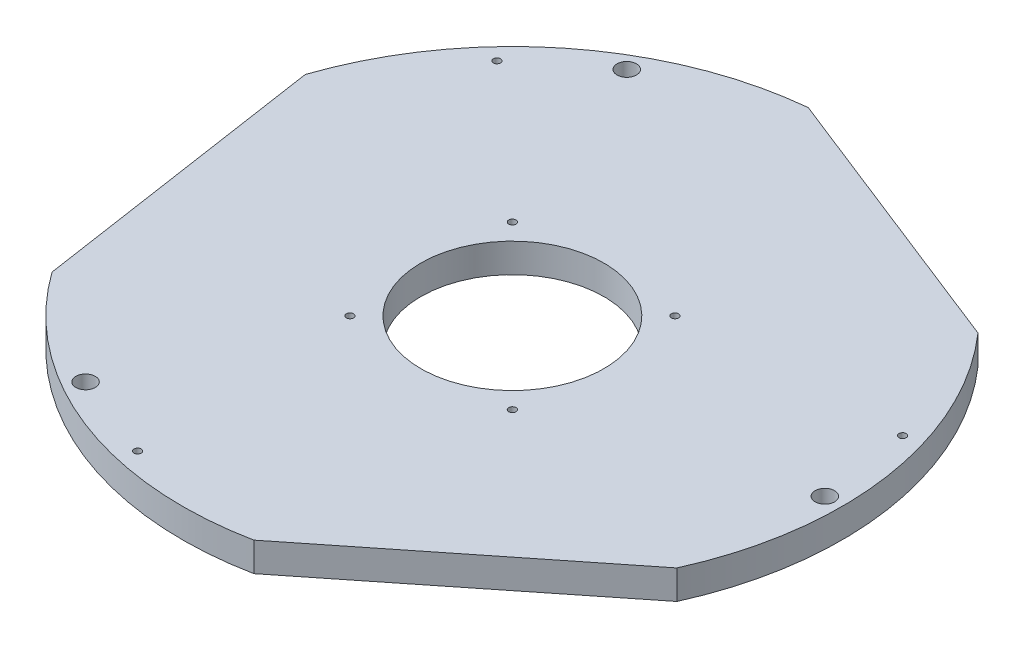
SolidWorks part; units mm, degrees
material "Oak"
ref_plane "Front Plane" through (0, 0, 0) normal (0, 0, 1) x (1, 0, 0)
ref_plane "Top Plane" through (0, 0, 0) normal (0, 1, 0) x (1, 0, 0)
ref_plane "Right Plane" through (0, 0, 0) normal (1, 0, 0) x (0, 0, -1)
sketch "Sketch1" plane through (0, 0, 0) normal (0, 0, 1) x (1, 0, 0)
  line L0 (0, -200000) -> (0, 218797.9879) construction
  line L1 (144.145, -22.3802) -> (144.145, -35.0802) construction
  line L2 (0, -22.3802) -> (144.145, -22.3802) construction
  line L3 (144.145, -35.0802) -> (0, -35.0802) construction
  line L4 (0, -200000) -> (0, 218797.9879) construction
  line L5 (144.145, -22.3802) -> (144.145, -35.0802)
  line L6 (0, -22.3802) -> (144.145, -22.3802)
  line L7 (144.145, -35.0802) -> (0, -35.0802)
  line L8 (0, -22.3802) -> (0, -35.0802)
revolve "Revolve1" add sketch "Sketch1" angle 360 about L4
hole_wizard "1/8 (0.125) Diameter Hole1" positions "Sketch2" profile "Sketch3" hole size "1/8" standard "ANSI Inch" end condition up to next
sketch "Sketch2" plane through (0, -22.3802, 0) normal (0, 1, 0) x (1, 0, 0)
  line L0 (0, 0) -> (136.525, 0) construction
  line L3 (0, 0) -> (-68.2625, -118.2341) construction
  line L6 (0, 0) -> (-68.2625, 118.2341) construction
  line L7 (-99.8481, 93.1098) -> (0, 0) construction
  line L9 (0, 0) -> (-30.7114, -133.0259) construction
  line L12 (0, 0) -> (130.5595, 39.916) construction
  line L14 (-35.5, -35.5) -> (35.5, -35.5) construction
  line L15 (-35.5, -35.5) -> (-35.5, 35.5) construction
  line L16 (-35.5, 35.5) -> (35.5, 35.5) construction
  line L17 (35.5, -35.5) -> (35.5, 35.5) construction
  line L18 (-35.5, 0) -> (0, 0) construction
  line L19 (0, 0) -> (0, -35.5) construction
  circle A0 centre (0, 0) radius 136.525
  point P0 (136.525, 0)
  point P2 (-68.2625, -118.2341)
  point P4 (-68.2625, 118.2341)
  point P32 (-99.8481, 93.1098)
  point P57 (130.5595, 39.916)
  point P60 (-30.7114, -133.0259)
  point P138 (-35.5, -35.5)
  point P141 (-35.5, 35.5)
  point P144 (35.5, 35.5)
  point P147 (35.5, -35.5)
  dimension "D3" = 17
  dimension "D1" = 120
  dimension "D2" = 120
  dimension "D4" = 120
  dimension "D5" = 120
  dimension "D6" = 71
sketch "Sketch3" plane through (136.525, -22.3802, 0) normal (1, 0, 0) x (0, 0, 1)
  line L0 (0, 0) -> (0, 12.7)
  line L1 (0, 12.7) -> (1.5875, 12.7)
  line L2 (1.5875, 12.7) -> (1.5875, 0)
  line L5 (1.5875, 0) -> (0, 0)
  line L11 (0, -6.35) -> (0, 107.95) construction
  dimension "Thru Hole Dia." = 3.175
  dimension "Thru Hole Depth" = 12.7
sketch "Sketch4" plane through (0, -22.3802, 0) normal (0, 1, 0) x (1, 0, 0)
  line L0 (253.7221, 37.919) -> (-94.0222, -238.6893)
  line L1 (-94.0222, -238.6893) -> (-159.6999, 200.7703)
  line L2 (-159.6999, 200.7703) -> (253.7221, 37.919)
  line L3 (253.7221, 37.919) -> (0, 0) construction
  line L4 (130.5595, 39.916) -> (136.525, 0) construction
  circle A0 centre (0, 0) radius 128.27 construction
  point P6 (133.5423, 19.958)
  dimension "D1" = 256.54
extrude "Cut-Extrude1" cut sketch "Sketch4" against normal through all flip side to cut
sketch "Sketch6" plane through (0, -22.3802, 0) normal (0, 1, 0) x (1, 0, 0)
  circle A0 centre (0, 0) radius 40
  dimension "D1" = 80
extrude "Cut-Extrude2" cut sketch "Sketch6" against normal through all
hole_wizard "M10x1.5 Tapped Hole1" positions "Sketch7" profile "Sketch8" tap size "M10x1.5" standard "ANSI Metric" end condition through all
sketch "Sketch7" plane through (0, -22.3802, 0) normal (0, 1, 0) x (1, 0, 0)
  point P0 (-68.2625, 118.2341)
  point P4 (136.525, 0)
  point P8 (-68.2625, -118.2341)
sketch "Sketch8" plane through (-68.2625, -22.3802, -118.2341) normal (1, 0, 0) x (0, 0, 1)
  line L0 (0, 0) -> (0, 12.7)
  line L1 (0, 12.7) -> (4.25, 12.7)
  line L2 (4.25, 12.7) -> (4.25, 0)
  line L5 (4.25, 0) -> (0, 0)
  line L11 (0, -6.35) -> (0, 107.95) construction
  dimension "Thru Tap Drill Dia." = 8.5
  dimension "Thru Tap Drill Depth" = 12.7
cosmetic thread "Hole Thread1" parameters "D2"=10
cosmetic thread "Hole Thread2" parameters "D2"=10
cosmetic thread "Hole Thread3" parameters "D2"=10
